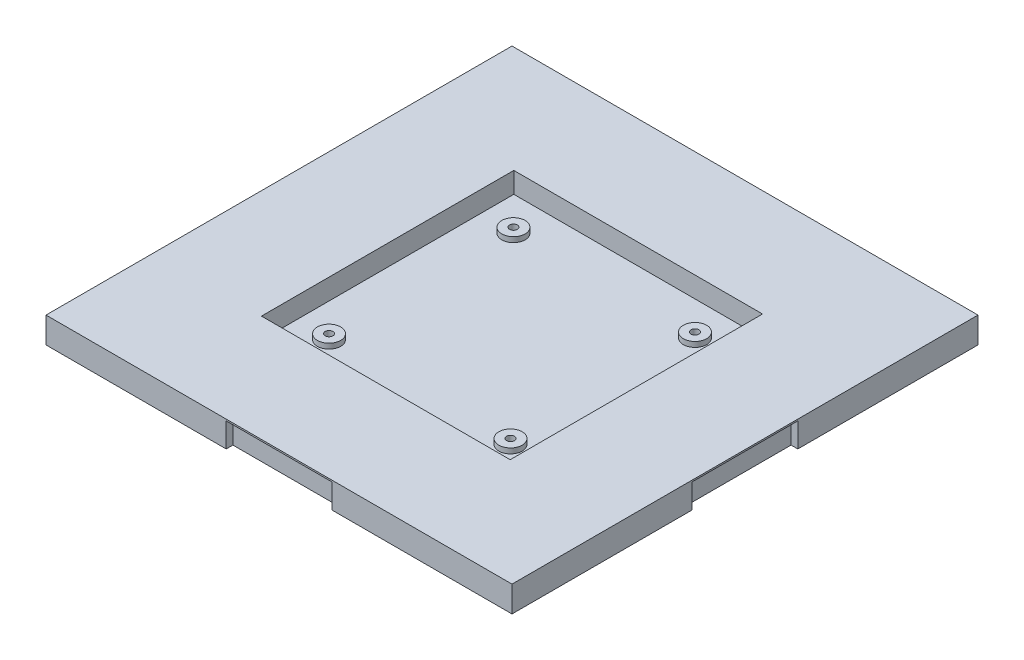
SolidWorks part; units mm, degrees
note: The reader was unsure of these and kept them because the rebuilt part matched: shared geometry of "Sketch1<3>", "Sketch1<5>", "Sketch1<6>".
ref_plane "Front Plane" through (0, 0, 0) normal (0, 0, 1) x (1, 0, 0)
ref_plane "Top Plane" through (0, 0, 0) normal (0, 1, 0) x (1, 0, 0)
ref_plane "Right Plane" through (0, 0, 0) normal (1, 0, 0) x (0, 0, -1)
sketch "Sketch1" plane through (0, 0, 0) normal (0, 1, 0) x (1, 0, 0)
  line L0 (-38.0365, 38.735) -> (38.0365, 38.735)
  line L1 (38.0365, 38.735) -> (38.0365, -38.735)
  line L2 (38.0365, -38.735) -> (-38.0365, -38.735)
  line L3 (-38.0365, -38.735) -> (-38.0365, 38.735)
  line L4 (-48.0365, 48.735) -> (48.0365, 48.735)
  line L5 (-90, 90) -> (90, 90)
  line L6 (-90, 90) -> (-90, -90)
  line L7 (-90, -90) -> (90, -90)
  line L8 (90, 90) -> (90, -90)
  line L9 (48.0365, 48.735) -> (48.0365, -48.735)
  line L10 (48.0365, -48.735) -> (-48.0365, -48.735)
  line L11 (-48.0365, -48.735) -> (-48.0365, 48.735)
  circle A0 centre (-35.1155, 35.687) radius 1.5
  circle A1 centre (34.9909, 35.687) radius 1.5
  circle A2 centre (34.9909, -35.5589) radius 1.5
  circle A3 centre (-35.1155, -35.5589) radius 1.5
  circle A4 centre (-35.1155, 35.687) radius 4.5
  circle A5 centre (34.9909, 35.687) radius 4.5
  circle A6 centre (34.9909, -35.5589) radius 4.5
  circle A7 centre (-35.1155, -35.5589) radius 4.5
  point P12 (0, -38.735)
  point P13 (-38.0365, 0)
  point P19 (-90, 0)
  point P20 (0, -90)
  dimension "D1" = 3
  dimension "D2" = 3.048
  dimension "D6" = 3
  dimension "D7" = 3.048
  dimension "D9" = 3.0456
  dimension "D11" = 3
  dimension "D12" = 3
  dimension "D13" = 3.1761
  dimension "D18" = 9
  dimension "D19" = 9
  dimension "D20" = 9
  dimension "D21" = 9
  dimension "D3" = 2.921
  dimension "D4" = 77.47
  dimension "D5" = 76.073
  dimension "D8" = 3.0456
  dimension "D10" = 3.1761
  dimension "D14" = 2.921
  dimension "D15" = 180
  dimension "D16" = 180
  dimension "D17" = 10
extrude "Boss-Extrude1" add sketch "Sketch1" along normal blind 10 contours L8 L5 L6 L7 L2 L3 L0 L1
extrude "Boss-Extrude2" add sketch "Sketch1<3>" along normal blind 2 contours L3 L2 L1 L0 A1 A0 A2 A3 | L11 L10 L9 L4 L2 L3 L0 L1
sketch "Sketch1<3>" plane through (0, 0, 0) normal (0, 1, 0) x (1, 0, 0) same geometry as "Sketch1"
extrude "Boss-Extrude3" add sketch "Sketch1<5>" along normal blind 4 contours A0 | A1 | A3 | A2 | L3 A7 L2 | L2 A7 L3 A3 | L1 A6 L2 A2 | L2 A6 L1 | L3 A4 L0 A0 | L0 A4 L3 | L0 A5 L1 A1 | L1 A5 L0
sketch "Sketch1<5>" plane through (0, 0, 0) normal (0, 1, 0) x (1, 0, 0) same geometry as "Sketch1"
extrude "Cut-Extrude1" cut sketch "Sketch1<6>" against normal blind 2.5 from surface at 4 contours A0 | A1 | A2 | A3 starting at face at (-35.1155, 4, -31.187)
sketch "Sketch1<6>" plane through (0, 0, 0) normal (0, 1, 0) x (1, 0, 0) same geometry as "Sketch1"
sketch "Sketch2" plane through (0, 10, 0) normal (0, 1, 0) x (1, 0, 0)
  line L0 (61.7104, -16.6911) -> (61.7104, 23.3089)
  line L1 (61.7104, -16.6911) -> (81.7104, -16.6911)
  line L2 (81.7104, -16.6911) -> (81.7104, 23.3089)
  line L3 (61.7104, 23.3089) -> (81.7104, 23.3089)
  line L8 (61.7104, 18.3089) -> (81.7104, 18.3089)
  line L9 (61.7104, -11.6911) -> (81.7104, -11.6911)
  line L10 (68.7104, 23.3089) -> (68.7104, 18.3089)
  line L11 (74.7104, 23.3089) -> (74.7104, 18.3089)
  line L12 (68.7104, -11.6911) -> (68.7104, -16.6911)
  line L13 (74.7104, -11.6911) -> (74.7104, -16.6911)
  line L14 (60.7104, -17.6911) -> (60.7104, 24.3089)
  line L15 (60.7104, 24.3089) -> (82.7104, 24.3089)
  line L16 (82.7104, -17.6911) -> (82.7104, 24.3089)
  line L17 (60.7104, -17.6911) -> (82.7104, -17.6911)
  circle A1 centre (63.9604, -14.4411) radius 1.25
  circle A2 centre (79.4604, -14.4411) radius 1.25
  circle A3 centre (79.4604, 21.0589) radius 1.25
  circle A4 centre (63.9604, 21.0589) radius 1.25
  dimension "D1" = 40
  dimension "D3" = 2.5
  dimension "D8" = 2.5
  dimension "D11" = 2.5
  dimension "D14" = 2.5
  dimension "D2" = 20
  dimension "D4" = 2.25
  dimension "D5" = 2.25
  dimension "D6" = 5
  dimension "D7" = 5
  dimension "D9" = 2.25
  dimension "D10" = 2.25
  dimension "D12" = 2.25
  dimension "D13" = 2.25
  dimension "D15" = 2.25
  dimension "D16" = 2.25
  dimension "D17" = 7
  dimension "D18" = 7
  dimension "D19" = 7
  dimension "D20" = 7
  dimension "D21" = 1
sketch "Sketch4" plane through (0, 0, -90) normal (0, 0, -1) x (-1, 0, 0)
  line L0 (20, -2.5) -> (20, 2.5) construction
  line L1 (-20, 9) -> (20, 9)
  line L2 (-20, 9) -> (-20, 0)
  line L3 (-20, 0) -> (20, 0)
  line L4 (20, 9) -> (20, 0)
  line L5 (-20.4, 9.4) -> (-20.4, -0.4)
  line L6 (-20.4, -0.4) -> (20.4, -0.4)
  line L7 (20.4, 9.4) -> (20.4, -0.4)
  line L8 (-20.4, 9.4) -> (20.4, 9.4)
  line M5 (-90, 0) -> (90, 0)
  dimension "D1" = 0.4
extrude "Cut-Extrude3" cut sketch "Sketch4" against normal blind 2.6 contours L8 L5 L2 L1 L4 L7 M5 | L4 L1 L2 M5
pattern_circular "CirPattern2" count 4 over 360 about axis through (0.0017, 0, 0.0018) along (0, 1, 0) of "Cut-Extrude3"
